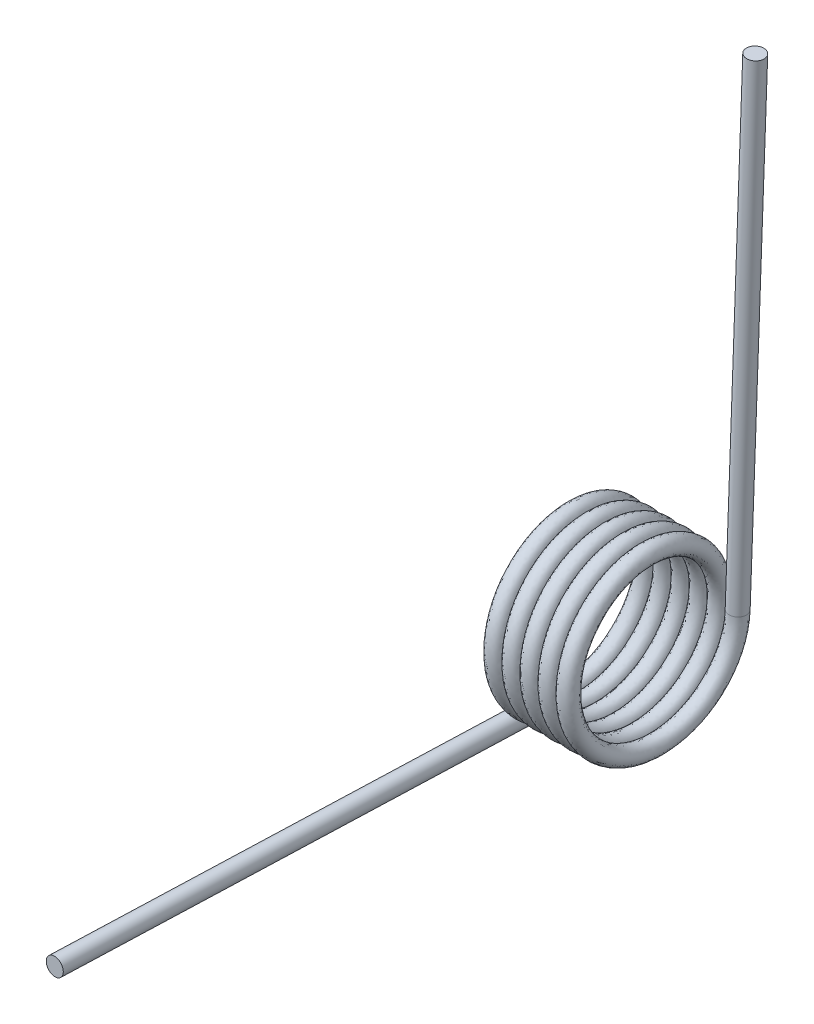
SolidWorks part; units mm, degrees
note: '?' marks a value the reader was unsure of.
ref_plane "Front Plane" through (0, 0, 0) normal (0, 0, 1) x (1, 0, 0)
ref_plane "Top Plane" through (0, 0, 0) normal (0, 1, 0) x (1, 0, 0)
ref_plane "Right Plane" through (0, 0, 0) normal (1, 0, 0) x (0, 0, -1)
sketch "Sketch1" plane through (0, 0, 0) normal (1, 0, 0) x (0, 0, -1)
  line L0 (5.1816, 0) -> (5.1816, 31.75) construction
  line L1 (0, -5.1816) -> (-31.75, -5.1816) construction
  line L2 (-31.75, -4.6101) -> (-31.75, -5.7531) construction
  circle A0 centre (0, 0) radius 5.7531 construction
  circle A1 centre (0, 0) radius 3.9624 construction
  circle A2 centre (0, -5.1816) radius 0.5715 construction
  circle A3 centre (0, 0) radius 5.1816 construction
  circle A4 centre (0, 0) radius 4.6101 construction
  point P10 (0, -4.6101)
  point P13 (5.1816, 0)
  point P16 (-31.75, -5.1816)
  dimension "OD" = 11.5062
  dimension "For Shaft Diameter" = 7.9248
  dimension "Wire Diameter" = 1.143
  dimension "Leg Length" = 31.75
sketch "Sketch2" plane through (0, 0, 0) normal (0, 0, 1) x (1, 0, 0)
  line L0 (-5.7277, 0) -> (0.5715, 0) construction
  circle A0 centre (0, 0) radius 0.5715 construction
  dimension "D1" = 1.143
  dimension "Spring Length at Maximum Torque" = 6.2992
sketch "Sketch3" plane through (0, 0, 0) normal (1, 0, 0) x (0, 0, -1)
  circle A0 centre (0, 0) radius 5.1816
curve "Helix/Spiral1" pitch 1.1684 height 6.1341 turns 5.25
ref_plane "Plane1" through (0, 0, -5.1816) normal (-0.0359, -0.9994, 0) x (0.9994, -0.0359, 0)
sketch "Sketch4" plane through (0, 0, 7.0993) normal (-0.0359, -0.9994, 0) x (-0.9994, 0.0359, 0)
  circle A0 centre (0, 12.2809) radius 0.5715
  dimension "D1" = 1.143
sweep "Sweep1" add profiles "Sketch4" path "Helix/Spiral1"
sketch "Sketch5" plane through (-0.0079, 0, 0.2199) normal (-0.0359, 0, 0.9994) x (0.9994, 0, 0.0359)
  circle A1 centre (-6.1302, -5.1816) radius 0.5715
  circle A2 centre (-6.1302, -5.1816) radius 0.5715
  dimension "D1" = 0
extrude "Boss-Extrude1" add sketch "Sketch5" along normal blind 31.75
sketch "Sketch6" plane through (0, 0, 0) normal (0.0359, 0.9994, 0) x (0.9994, -0.0359, 0)
  circle A1 centre (0, 5.1816) radius 0.5715
  circle A2 centre (0, 5.1816) radius 0.5715
  dimension "D1" = 0
extrude "Boss-Extrude2" add sketch "Sketch6" along normal blind 31.75
ref_axis "Axis1" through (2.1875, 0, 0) along (-1, 0, 0)?
equation "\"D1@Sketch4\"=\"Wire Diameter@Sketch1\""
equation "\"D1@Sketch2\"=\"Wire Diameter@Sketch1\""
equation "\"D1@Boss-Extrude1\" = \"Leg Length@Sketch1\""
equation "\"D1@Boss-Extrude2\"=\"Leg Length@Sketch1\""
equation "\"D4@Helix/Spiral1\"=\"Wire Diameter@Sketch1\"+.001"
